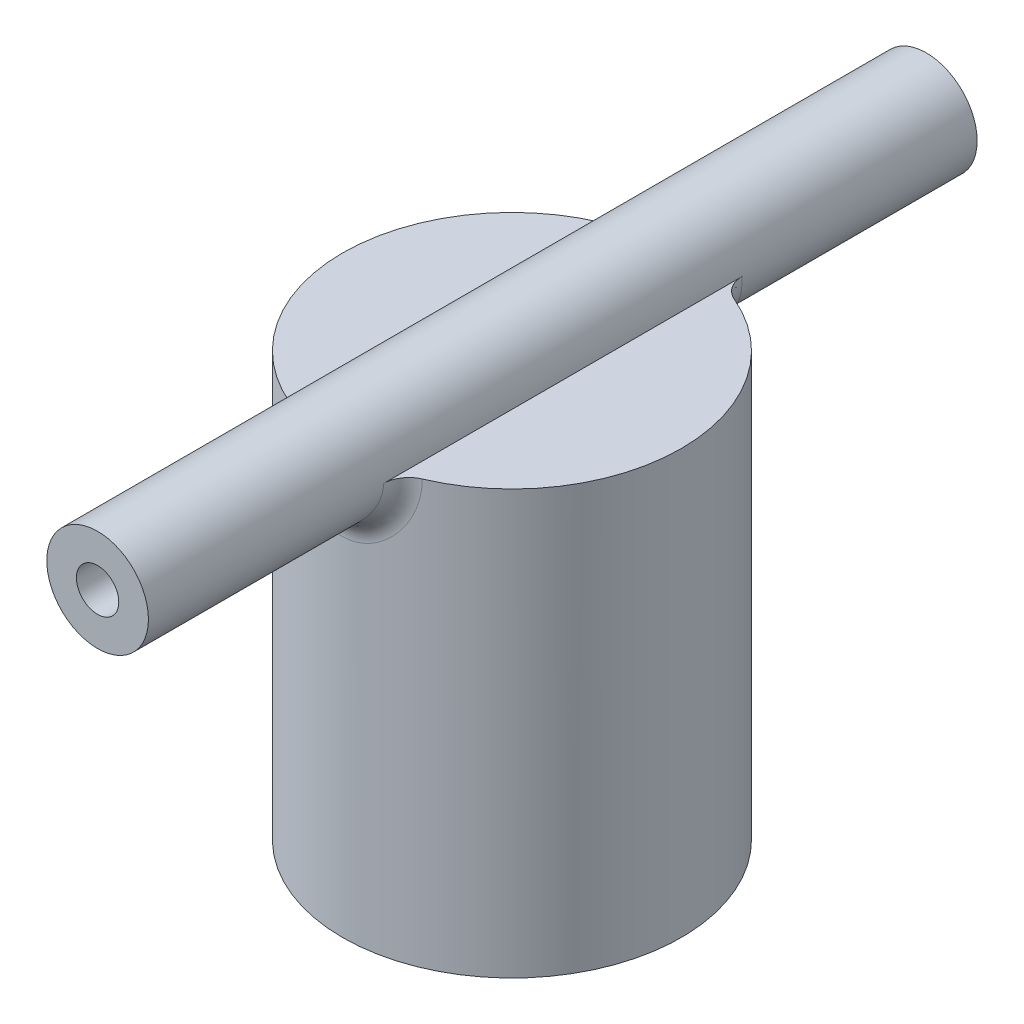
SolidWorks part; units mm, degrees
ref_plane "Front Plane" through (0, 0, 0) normal (0, 0, 1) x (1, 0, 0)
ref_plane "Top Plane" through (0, 0, 0) normal (0, 1, 0) x (1, 0, 0)
ref_plane "Right Plane" through (0, 0, 0) normal (1, 0, 0) x (0, 0, -1)
sketch "Sketch1" plane through (0, 0, 0) normal (0, 1, 0) x (1, 0, 0)
  circle A0 centre (0, 0) radius 20
  dimension "D1" = 40
extrude "Boss-Extrude1" add sketch "Sketch1" along normal blind 50 contours A0
sketch "Sketch2" plane through (0, 0, 0) normal (0, 0, 1) x (1, 0, 0)
  line L0 (20, 50) -> (-20, 50) construction
  circle A0 centre (0, 50) radius 6
  dimension "D1" = 12
extrude "Boss-Extrude2" add sketch "Sketch2" along normal mid plane 97.84
fillet "Fillet1" radius 3 2 edges at (0.891, 44.0665, -19.9801) (-1.4259, 44.1719, 19.9491)
ref_plane "Plane1" through (0, 30, 0) normal (0, 1, 0) x (1, 0, 0)
sketch "Sketch3" plane through (0, 0, 48.92) normal (0, 0, 1) x (1, 0, 0)
  circle A0 centre (0, 50) radius 2.5
  point P2 (0, 50)
  dimension "D1" = 5
extrude "Cut-Extrude1" cut sketch "Sketch3" against normal through all
